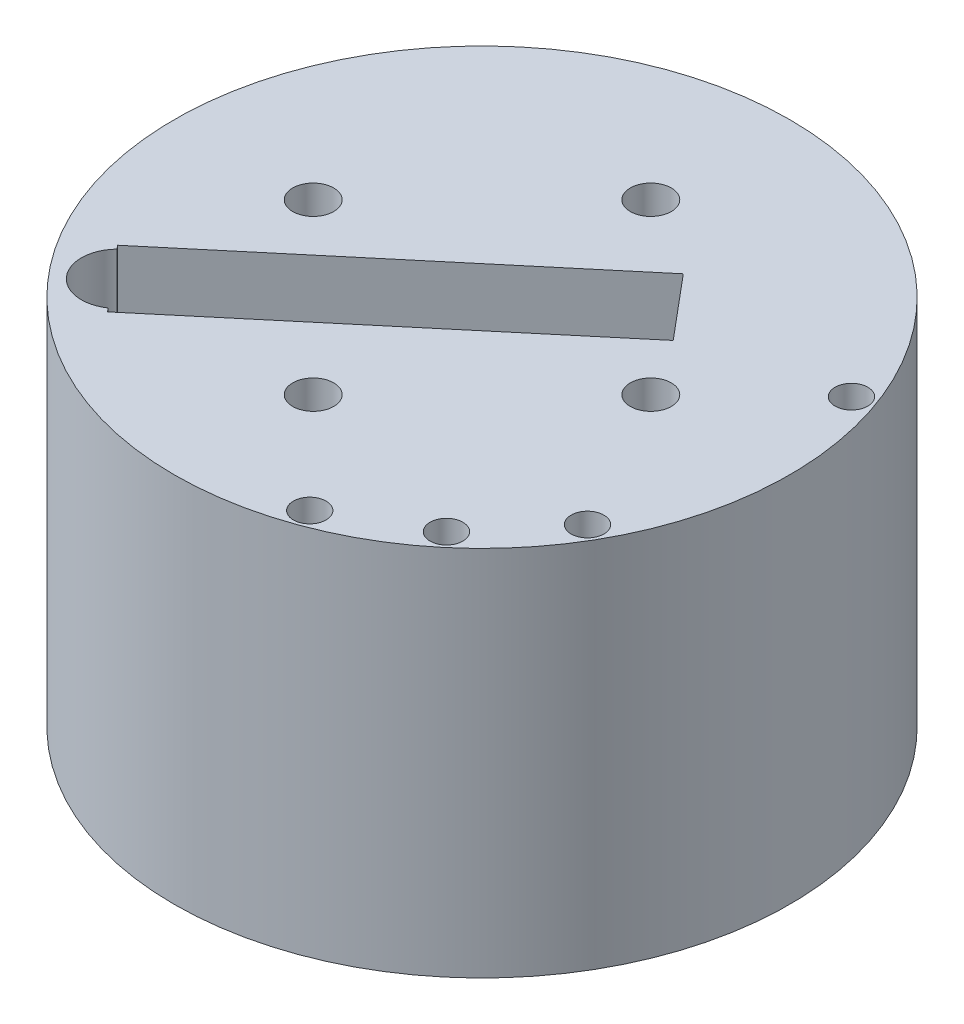
SolidWorks part; units mm, degrees
material "AISI 1010 Steel, hot rolled bar"
ref_plane "Front Plane" through (0, 0, 0) normal (0, 0, 1) x (1, 0, 0)
ref_plane "Top Plane" through (0, 0, 0) normal (0, 1, 0) x (1, 0, 0)
ref_plane "Right Plane" through (0, 0, 0) normal (1, 0, 0) x (0, 0, -1)
sketch "Sketch2" plane through (0, 0, 0) normal (0, 1, 0) x (1, 0, 0)
  circle A0 centre (0, 0) radius 47.6885
  dimension "D1" = 95.377
extrude "Boss-Extrude1" add sketch "Sketch2" along normal blind 57.658
sketch "Sketch4" plane through (0, 57.658, 0) normal (0, 1, 0) x (1, 0, 0)
  circle A1 centre (-26.162, 0) radius 3.175
  circle A2 centre (26.162, 0) radius 3.175
  circle A3 centre (0, 26.162) radius 3.175
  circle A4 centre (0, -26.162) radius 3.175
sketch "Sketch5" plane through (0, 57.658, 0) normal (0, 1, 0) x (1, 0, 0)
  line L2 (0, 0) -> (-42.4665, -13.8681)
  line L4 (0, 0) -> (-30.6943, -25.7555)
  circle A2 centre (0, 0) radius 44.6736
  circle A9 centre (-30.6943, -25.7555) radius 5.6388
  dimension "D3" = 11.2776
  dimension "D5" = 89.3472
  dimension "D6" = 21.915
  dimension "D4" = 40.0685
extrude "Cut-Extrude2" cut sketch "Sketch5" against normal through all contours A9
extrude "Cut-Extrude3" cut sketch "Sketch4" against normal through all
sketch "Sketch6" plane through (0, 57.658, 0) normal (0, 1, 0) x (1, 0, 0)
  line L1 (-27.0503, -30.9873) -> (20.6206, 9.0134)
  line L2 (-27.0503, -30.9873) -> (-35.2137, -21.2585)
  line L3 (-35.2137, -21.2585) -> (12.4572, 18.7422)
  line L4 (20.6206, 9.0134) -> (12.4572, 18.7422)
  dimension "D1" = 62.23
  dimension "D2" = 12.7
  dimension "D3" = 6.35
  dimension "D4" = 21.59
  dimension "D5" = 90
  dimension "D6" = 90
  dimension "D7" = 90
extrude "Cut-Extrude4" cut sketch "Sketch6" against normal blind 43.18
sketch "Sketch11" plane through (0, 0, 0) normal (0, -1, 0) x (1, 0, 0)
  circle A0 centre (0, 26.162) radius 6.35
  circle A1 centre (26.162, 0) radius 6.35
  circle A2 centre (0, -26.162) radius 6.35
  circle A3 centre (-26.162, 0) radius 6.35
  dimension "D1" = 12.7
  dimension "D2" = 12.7
  dimension "D3" = 12.7
  dimension "D4" = 12.7
extrude "Cut-Extrude7" cut sketch "Sketch11" against normal blind 7.62
sketch "Sketch14" plane through (0, 0, 0) normal (0, -1, 0) x (1, 0, 0)
  circle A0 centre (1.3569, -14.949) radius 2.067
  circle A1 centre (4.5237, 8.9723) radius 2.067
extrude "Cut-Extrude8" cut sketch "Sketch14" against normal blind 19.05
sketch "Sketch15" plane through (0, 0, 0) normal (0, -1, 0) x (1, 0, 0)
  line L0 (47.6885, 0) -> (-47.6885, 0)
  line L1 (0, -47.6885) -> (0, 47.6885)
  line L2 (-30.6943, 25.7555) -> (0, 0)
  line L5 (0, 0) -> (28.7156, 34.222)
  line L6 (0, 0) -> (38.6885, 22.3368)
  line L7 (0, 0) -> (15.2793, 41.9794)
  line L8 (0, 0) -> (41.9794, -15.2793)
  circle A0 centre (0, 0) radius 47.6885 construction
  circle A1 centre (1.3569, -14.949) radius 2.067 construction
  circle A2 centre (1.3569, -14.949) radius 2.067 construction
  circle A3 centre (4.5237, 8.9723) radius 2.067 construction
  circle A4 centre (28.7156, 34.222) radius 2.54
  circle A5 centre (38.6885, 22.3368) radius 2.54
  circle A6 centre (15.2793, 41.9794) radius 2.54
  circle A7 centre (41.9794, -15.2793) radius 2.54
  point P9 (0, 0)
  point P29 (-44.6487, -1.4926)
  dimension "D1" = 1.3569
  dimension "D2" = 14.949
  dimension "D3" = 8.9723
  dimension "D4" = 4.5237
  dimension "D6" = 40
  dimension "D7" = 44.6736
  dimension "D10" = 50
  dimension "D5" = 40.0685
  dimension "D8" = 20
  dimension "D9" = 20
extrude "Cut-Extrude10" cut sketch "Sketch15" against normal blind 84.074 contours A4 | A6 | A5 | A7
equation "\"D4@Sketch5\"=(3.755/2)-(0.5/2)-0.05"
equation "\"D1@Sketch6\"=2.10 + (0.85-0.5)"
